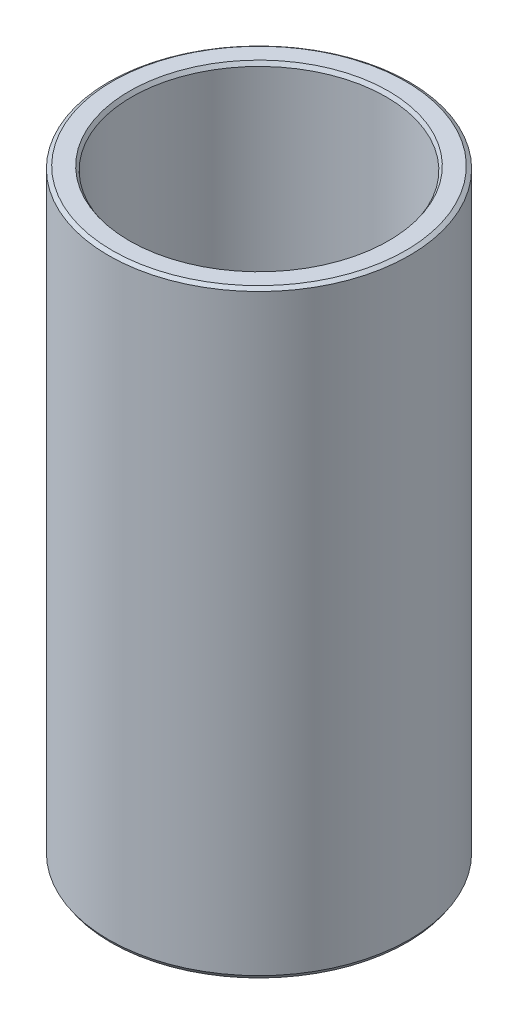
SolidWorks part; units mm, degrees
ref_plane "Front Plane" through (0, 0, 0) normal (0, 0, 1) x (1, 0, 0)
ref_plane "Top Plane" through (0, 0, 0) normal (0, 1, 0) x (1, 0, 0)
ref_plane "Right Plane" through (0, 0, 0) normal (1, 0, 0) x (0, 0, -1)
sketch "Sketch1" plane through (0, 0, 0) normal (0, 1, 0) x (1, 0, 0)
  circle A0 centre (0, 0) radius 60
  dimension "SLEEVE_OD" = 120
extrude "Boss-Extrude1" add sketch "Sketch1" along normal blind 238.8857
sketch "Sketch2" plane through (0, 0, 0) normal (0, 1, 0) x (1, 0, 0)
  circle A0 centre (0, 0) radius 50.7534
  dimension "BORE_D" = 101.5068
extrude "Cut-Extrude1" cut sketch "Sketch2" along normal through all
chamfer "Chamfer1" distance 0.9785 angle 56.832 4 edges at (0, 238.8857, 50.7534) (0, 0, 50.7534) (0, 0, 60) (0, 238.8857, 60) first distance on face at (0, 238.8857, 50.7534) first distance on face at (0, 0, 50.7534) first distance on face at (0, 238.8857, 60)
